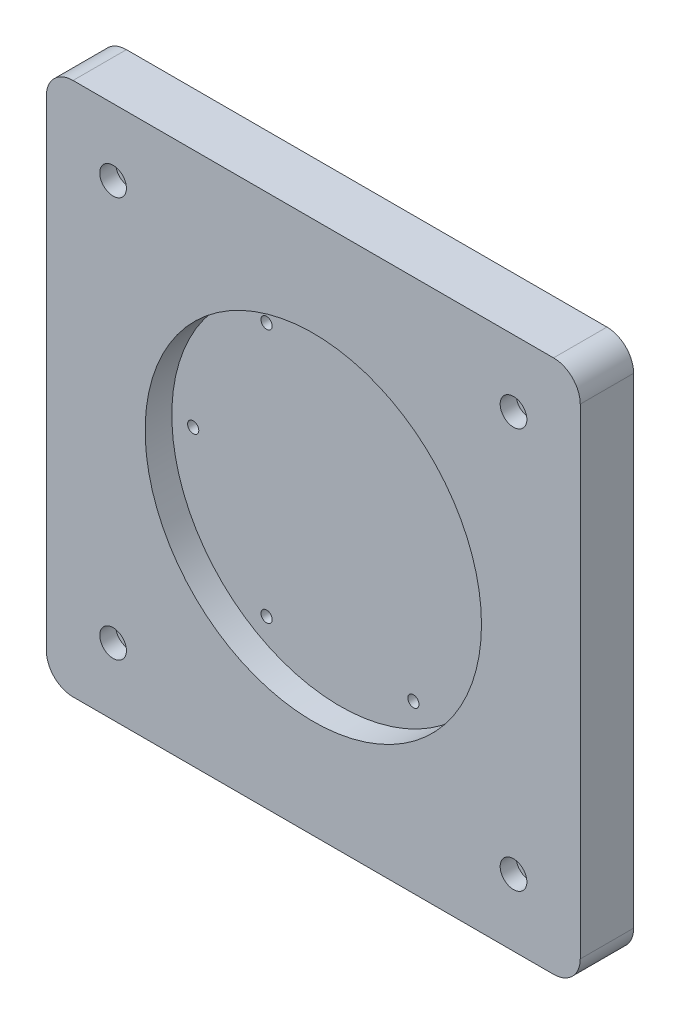
SolidWorks part; units mm, degrees
material "6063-O"
ref_plane "正面" through (0, 0, 0) normal (0, 0, 1) x (1, 0, 0)
ref_plane "平面" through (0, 0, 0) normal (0, 1, 0) x (1, 0, 0)
ref_plane "右側面" through (0, 0, 0) normal (1, 0, 0) x (0, 0, -1)
sketch "ｽｹｯﾁ1" plane through (0, 0, 0) normal (0, 0, 1) x (1, 0, 0)
  line L1 (-100, 100) -> (100, 100)
  line L2 (-100, 100) -> (-100, -100)
  line L3 (-100, -100) -> (100, -100)
  line L4 (100, 100) -> (100, -100)
  line L5 (-100, 100) -> (100, -100) construction
  line L6 (-100, -100) -> (100, 100) construction
  circle A0 centre (0, 0) radius 63
  point P0 (0, 0)
  dimension "D1" = 126
  dimension "D2" = 200
  dimension "D3" = 200
extrude "ﾎﾞｽ - 押し出し1" add sketch "ｽｹｯﾁ1" along normal blind 10
sketch "ｽｹｯﾁ2" plane through (0, 0, 0) normal (0, 0, -1) x (-1, 0, 0)
  line L4 (-100, 100) -> (-100, -100)
  line L5 (-100, -100) -> (100, -100)
  line L6 (100, -100) -> (100, 100)
  line L7 (100, 100) -> (-100, 100)
  line L8 (-100, 100) -> (-100, -100)
  line L9 (-100, -100) -> (100, -100)
  line L10 (100, -100) -> (100, 100)
  line L11 (100, 100) -> (-100, 100)
  dimension "D1" = 0
extrude "ﾎﾞｽ - 押し出し2" add sketch "ｽｹｯﾁ2" along normal blind 10
sketch "ｽｹｯﾁ3" plane through (0, 0, 0) normal (0, 0, 1) x (1, 0, 0)
  line L0 (0, 0) -> (0, -63) construction
  line L1 (0, 0) -> (27.5, -47.6314) construction
  circle A0 centre (27.5, -47.6314) radius 2.1
  circle A1 centre (-27.5, -47.6314) radius 2.1
  circle A2 centre (-55, 0) radius 2.1
  circle A3 centre (-27.5, 47.6314) radius 2.1
  circle A4 centre (27.5, 47.6314) radius 2.1
  circle A5 centre (55, 0) radius 2.1
  circle A6 centre (0, 0) radius 63 construction
  point P0 (0, 0)
  point P15 (0, 0)
  point P17 (0, -55)
  point P18 (0, 0)
  point P19 (27.4669, -47.0984)
  dimension "D1" = 55
  dimension "D2" = 4.2
  dimension "D4" = 30
  dimension "D3" = 6
extrude "ｶｯﾄ - 押し出し1" cut sketch "ｽｹｯﾁ3" against normal blind 10
sketch "ｽｹｯﾁ4" plane through (0, 0, 10) normal (0, 0, 1) x (1, 0, 0)
  line L0 (100, 100) -> (-100, 100) construction
  line L1 (100, -100) -> (100, 100) construction
  circle A0 centre (75, 75) radius 2.75
  circle A1 centre (75, -75) radius 2.75
  circle A2 centre (-75, -75) radius 2.75
  circle A3 centre (-75, 75) radius 2.75
  point P15 (0, 0)
  dimension "D1" = 5.5
  dimension "D2" = 25
  dimension "D3" = 25
  dimension "D4" = 4
extrude "ｶｯﾄ - 押し出し2" cut sketch "ｽｹｯﾁ4" against normal through all
sketch "ｽｹｯﾁ5" plane through (0, 0, 10) normal (0, 0, 1) x (1, 0, 0)
  circle A0 centre (75, -75) radius 5
  circle A1 centre (-75, -75) radius 5
  circle A2 centre (-75, 75) radius 5
  circle A3 centre (75, 75) radius 5
  point P12 (0, 0)
  dimension "D1" = 10
  dimension "D2" = 4
extrude "ｶｯﾄ - 押し出し3" cut sketch "ｽｹｯﾁ5" against normal blind 6
fillet "ﾌｨﾚｯﾄ1" radius 10 4 edges at (-100, -100, 0) (100, -100, 0) (100, 100, 0) (-100, 100, 0)
